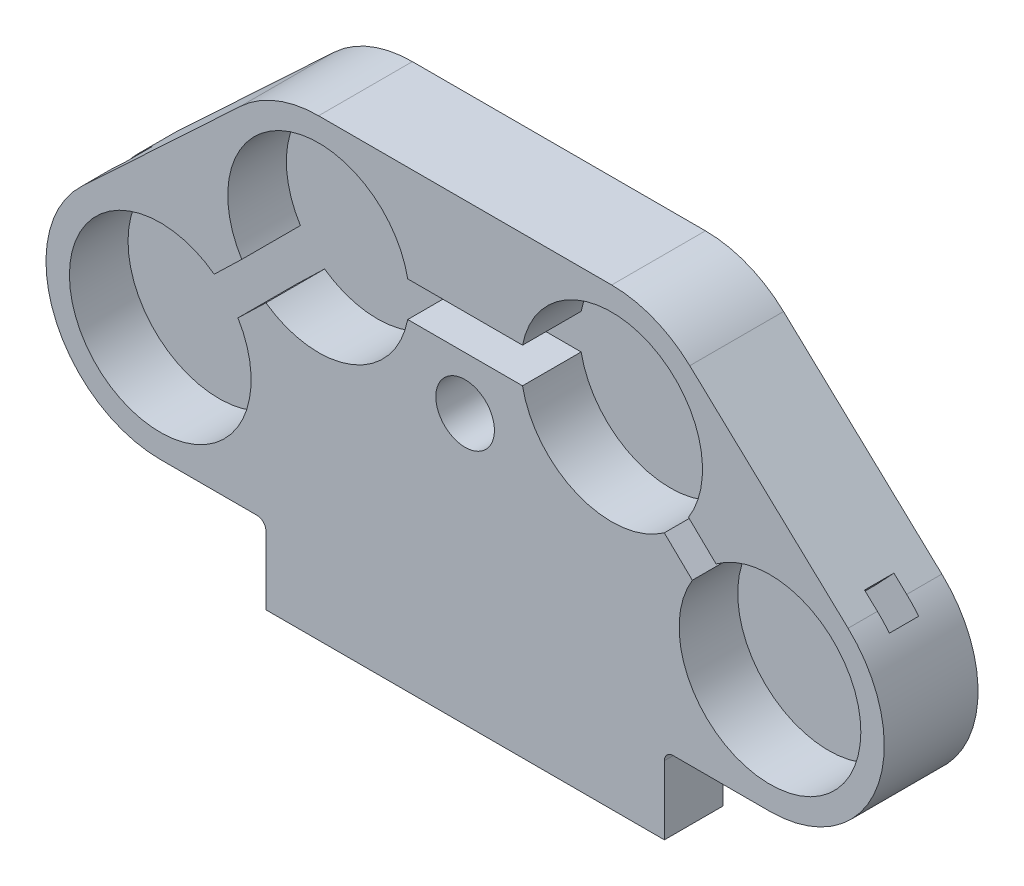
SolidWorks part; units mm, degrees
ref_plane "Front Plane" through (0, 0, 0) normal (0, 0, 1) x (1, 0, 0)
ref_plane "Top Plane" through (0, 0, 0) normal (0, 1, 0) x (1, 0, 0)
ref_plane "Right Plane" through (0, 0, 0) normal (1, 0, 0) x (0, 0, -1)
sketch "Sketch1" plane through (0, 0, 0) normal (0, 0, 1) x (1, 0, 0)
  line L0 (-11.9595, 12.7758) -> (-50.7466, -23.5332) construction
  line L1 (11.9595, 12.7758) -> (50.7466, -23.5332) construction
  line L2 (-11.9595, 12.7758) -> (11.9595, 12.7758) construction
  line L3 (-50.7466, -23.5332) -> (50.7466, -23.5332) construction
  line L4 (-17.5, -2) -> (17.5, -2) construction
  line L5 (0, 0) -> (0, -2) construction
  line L6 (-17.5, -2) -> (-17.5, 4) construction
  line L7 (-17.5, 4) -> (-20.5, 4) construction
  line L8 (-20.5, 4) -> (-20.5, -5) construction
  line L9 (-20.5, -5) -> (20.5, -5) construction
  line L10 (20.5, -5) -> (20.5, 4) construction
  line L11 (20.5, 4) -> (17.5, 4) construction
  line L12 (17.5, 4) -> (17.5, -2) construction
  line L13 (0, -2) -> (0, 40.1846) construction
  line L14 (-26.0058, 14.352) -> (-12.5, 26.995) construction
  line L15 (-32.669, 21.47) -> (-19.1632, 34.1129)
  line L16 (-26.0058, 4.602) -> (-17.75, 4.602)
  line L17 (-17, 3.852) -> (-17, -2)
  line L18 (-17, -2) -> (0, -2)
  line L19 (-12.5, 36.745) -> (0, 36.745)
  line L20 (0, 36.745) -> (0, -2)
  circle A0 centre (0, 0) radius 17.5 construction
  circle A1 centre (-26.0058, 14.352) radius 7.75
  circle A2 centre (-12.5, 26.995) radius 7.75
  circle A3 centre (-12.5, 26.995) radius 9.75 construction
  circle A4 centre (-26.0058, 14.352) radius 9.75 construction
  arc A5 (-17.75, 4.602) -> (-17, 3.852) centre (-17.75, 3.852) cw
  arc A6 (-19.1632, 34.1129) -> (-12.5, 36.745) centre (-12.5, 26.995) cw
  arc A7 (-26.0058, 4.602) -> (-32.669, 21.47) centre (-26.0058, 14.352) cw
  dimension "D1" = 35
  dimension "D8" = 15.5
  dimension "D10" = 3
  dimension "D11" = 2
  dimension "D13" = 0.75
  dimension "D2" = 93.78
  dimension "D3" = 35
  dimension "2" = 2
  dimension "D4" = 6
  dimension "D5" = 3
  dimension "D6" = 3
  dimension "D7" = 3
  dimension "D9" = 25
  dimension "D12" = 0.5
extrude "Boss-Extrude1" add sketch "Sketch1" along normal blind 5 contours A7 L16 A5 L17 L18 L20 L19 A6 L15 A2 A1 region at (-12.1141, 15.2891, 0)
mirror "Mirror1" about plane through (0, 0, 0) normal (1, 0, 0) of "Boss-Extrude1"
sketch "Sketch3" plane through (0, 0, 0) normal (0, 0, -1) x (-1, 0, 0)
  line L0 (32.669, 21.47) -> (19.1632, 34.1129) construction
  line L1 (32.669, 21.47) -> (19.1632, 34.1129)
  line L2 (12.5, 36.745) -> (-12.5, 36.745) construction
  line L3 (12.5, 36.745) -> (-12.5, 36.745)
  line L4 (-32.669, 21.47) -> (-19.1632, 34.1129) construction
  line L5 (-32.669, 21.47) -> (-19.1632, 34.1129)
  line L6 (-19.3426, 7.2341) -> (-5.8368, 19.877)
  line L7 (19.3426, 7.2341) -> (5.8368, 19.877)
  line L8 (-5.8368, 19.877) -> (-1.3668, 24.0615)
  line L9 (1.3668, 24.0615) -> (5.8368, 19.877)
  arc A0 (26.0058, 4.602) -> (32.669, 21.47) centre (26.0058, 14.352) ccw construction
  arc A1 (26.0058, 4.602) -> (32.669, 21.47) centre (26.0058, 14.352) ccw construction
  arc A2 (19.1632, 34.1129) -> (12.5, 36.745) centre (12.5, 26.995) ccw construction
  arc A3 (19.1632, 34.1129) -> (12.5, 36.745) centre (12.5, 26.995) ccw
  arc A4 (-12.5, 36.745) -> (-19.1632, 34.1129) centre (-12.5, 26.995) ccw construction
  arc A5 (-12.5, 36.745) -> (-19.1632, 34.1129) centre (-12.5, 26.995) ccw
  arc A6 (-32.669, 21.47) -> (-26.0058, 4.602) centre (-26.0058, 14.352) ccw construction
  arc A7 (-32.669, 21.47) -> (-26.0058, 4.602) centre (-26.0058, 14.352) ccw construction
  circle A8 centre (-26.0058, 14.352) radius 9.75 construction
  circle A9 centre (-12.5, 26.995) radius 9.75 construction
  circle A10 centre (12.5, 26.995) radius 9.75 construction
  circle A11 centre (26.0058, 14.352) radius 9.75 construction
  circle A12 centre (0, 13.6418) radius 8.5409 construction
  arc A13 (-5.8368, 19.877) -> (5.8368, 19.877) centre (0, 13.6418) cw construction
  arc A14 (-32.669, 21.47) -> (-19.3426, 7.2341) centre (-26.0058, 14.352) ccw
  arc A15 (32.669, 21.47) -> (19.3426, 7.2341) centre (26.0058, 14.352) cw
  arc A16 (-1.3668, 24.0615) -> (1.3668, 24.0615) centre (0, 22.6014) cw
  arc M9 (26.0058, 4.602) -> (32.669, 21.47) centre (26.0058, 14.352) ccw
  line M10 (32.669, 21.47) -> (19.1632, 34.1129)
  arc M11 (19.1632, 34.1129) -> (12.5, 36.745) centre (12.5, 26.995) ccw
  line M12 (12.5, 36.745) -> (-12.5, 36.745)
  arc M13 (-12.5, 36.745) -> (-19.1632, 34.1129) centre (-12.5, 26.995) ccw
  line M14 (-19.1632, 34.1129) -> (-32.669, 21.47)
  arc M15 (-32.669, 21.47) -> (-26.0058, 4.602) centre (-26.0058, 14.352) ccw
  circle M23 centre (12.5, 26.995) radius 7.75
  circle M24 centre (26.0058, 14.352) radius 7.75
  circle M25 centre (-12.5, 26.995) radius 7.75
  circle M26 centre (-26.0058, 14.352) radius 7.75
  dimension "D1" = 2
extrude "Boss-Extrude2" add sketch "Sketch3" along normal blind 3 contours A15 A14 L6 A13 L7 M9 M10 M11 M12 M13 M14 M15 M23 M25 M26 M24 | M26 | M25 | M23 | M24 region at (-34.3447, 11.058, 0) region at (-12.5, 26.995, 0) region at (-26.0058, 14.352, 0) region at (12.5, 26.995, 0) region at (26.0058, 14.352, 0)
sketch "Sketch4" plane through (0, 0, 0) normal (0, 0, 1) x (1, 0, 0)
  circle A0 centre (26.0058, 14.352) radius 7.75 construction
  circle A1 centre (12.5, 26.995) radius 7.75 construction
  circle A2 centre (-12.5, 26.995) radius 7.75 construction
  circle A3 centre (-26.0058, 14.352) radius 7.75 construction
  circle A4 centre (26.0058, 14.352) radius 7.75
  circle A5 centre (12.5, 26.995) radius 7.75
  circle A6 centre (-12.5, 26.995) radius 7.75
  circle A7 centre (-26.0058, 14.352) radius 7.75
extrude "Cut-Extrude1" [suppressed] cut sketch "Sketch4" against normal blind 1
sketch "Sketch5" plane through (0, 0, 5) normal (0, 0, 1) x (1, 0, 0)
  line L0 (-26.0058, 14.352) -> (-12.5, 26.995) construction
  line L1 (-17.1499, 24.6966) -> (-23.3682, 18.6909)
  line L2 (-23.3682, 18.6909) -> (-21.284, 16.533)
  line L3 (-21.284, 16.533) -> (-15.0658, 22.5387)
  line L4 (-15.0658, 22.5387) -> (-17.1499, 24.6966)
  line L5 (0, 0) -> (0, 28.253) construction
  line L6 (-12.5, 26.995) -> (12.5, 26.995) construction
  line L7 (-6.9065, 28.495) -> (8.5226, 28.495)
  line L8 (8.5226, 28.495) -> (8.5226, 25.495)
  line L9 (8.5226, 25.495) -> (-6.9065, 25.495)
  line L10 (-6.9065, 25.495) -> (-6.9065, 28.495)
  line L11 (21.284, 16.533) -> (15.0658, 22.5387)
  line L12 (23.3682, 18.6909) -> (21.284, 16.533)
  line L13 (17.1499, 24.6966) -> (23.3682, 18.6909)
  line L14 (15.0658, 22.5387) -> (17.1499, 24.6966)
  point P6 (-16.1078, 23.6176)
  point P16 (-6.9065, 26.995)
  dimension "D1" = 3
  dimension "D2" = 3
extrude "Cut-Extrude2" cut sketch "Sketch5" against normal up to surface (5 mm away) up to face at (-18.2558, 14.352, 0)
sketch "Sketch6" [suppressed] plane through (-25.9692, 27.7416, 0) normal (-0.6834, 0.73, 0) x (0.73, 0.6834, 0)
  line L0 (-16.9271, 1) -> (-1.556, 1) construction
  line L1 (-16.9271, 1) -> (-1.556, 1) construction
  line L2 (-9.1771, -5) -> (-9.1771, 4) construction
  line L3 (-7.6771, 1) -> (-10.6771, 1)
  line L4 (-7.6771, 1) -> (-7.6771, -1.5)
  line L5 (-7.6771, -1.5) -> (-10.6771, -1.5)
  line L6 (-10.6771, 1) -> (-10.6771, -1.5)
  point P8 (-9.1771, 1)
  dimension "D1" = 2.5
  dimension "D2" = 3
extrude "Cut-Extrude3" [suppressed] cut sketch "Sketch6" against normal blind 11
mirror "Mirror2" [suppressed] about plane through (0, 0, 0) normal (1, 0, 0)
sketch "Sketch7" plane through (-25.9692, 27.7416, 0) normal (-0.6834, 0.73, 0) x (0.73, 0.6834, 0)
  line L0 (-16.9271, 0) -> (-1.556, 0) construction
  line L1 (-7.6771, 0) -> (-10.6771, 0)
  line L2 (-7.6771, 0) -> (-7.6771, -2.5)
  line L3 (-7.6771, -2.5) -> (-10.6771, -2.5)
  line L4 (-10.6771, 0) -> (-10.6771, -2.5)
  line L5 (-16.9271, 0) -> (-1.556, 0) construction
  line L8 (-9.1771, -5) -> (-9.1771, 3) construction
  point P6 (-7.4615, 0)
  point P9 (-9.1771, -2.5)
  dimension "D1" = 3
  dimension "D2" = 2.5
extrude "Cut-Extrude4" cut sketch "Sketch7" against normal blind 10
mirror "Mirror3" about plane through (0, 0, 0) normal (1, 0, 0) of "Cut-Extrude4"
sketch "Sketch8" plane through (0, 0, 5) normal (0, 0, 1) x (1, 0, 0)
  circle A2 centre (0, 21) radius 3.75 construction
  circle A3 centre (0, 21) radius 2.5
  dimension "D1" = 7.5
  dimension "D2" = 5
  dimension "D3" = 21
extrude "Cut-Extrude5" cut sketch "Sketch8" against normal blind 10
